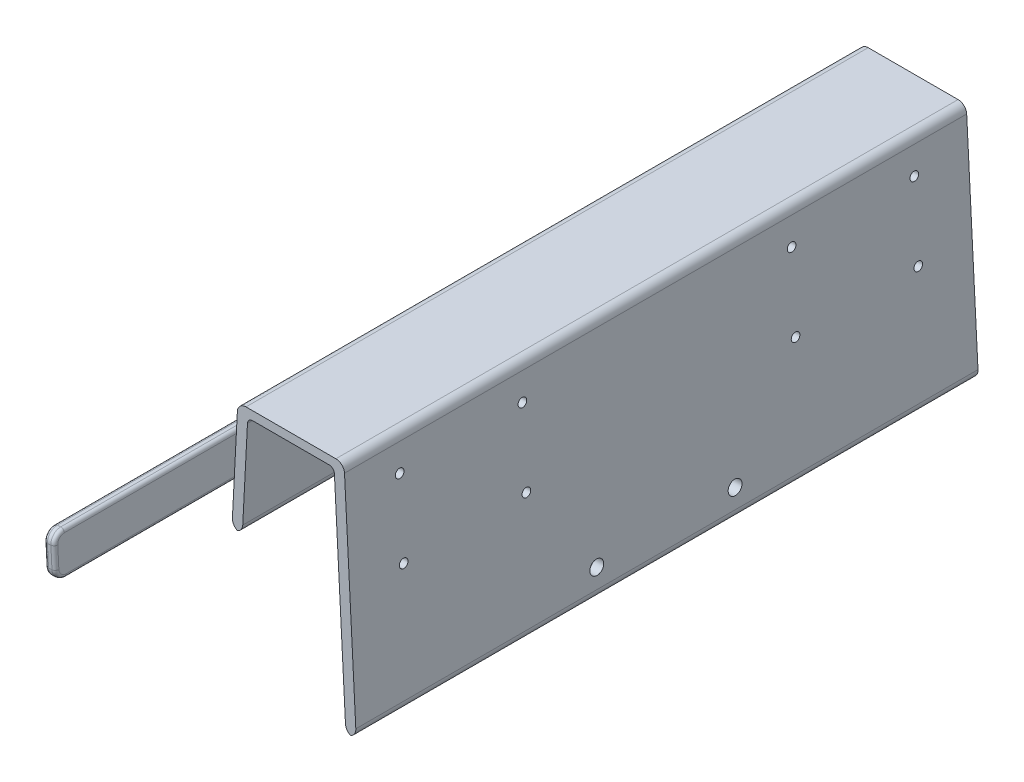
SolidWorks part; units mm, degrees
ref_plane "Front Plane" through (0, 0, 0) normal (0, 0, 1) x (1, 0, 0)
ref_plane "Top Plane" through (0, 0, 0) normal (0, 1, 0) x (1, 0, 0)
ref_plane "Right Plane" through (0, 0, 0) normal (1, 0, 0) x (0, 0, -1)
sketch "Sketch1" plane through (0, 0, 0) normal (0, 0, 1) x (1, 0, 0)
  line L0 (0, 0) -> (1.5701, 29.9589)
  line L1 (1.5701, 29.9589) -> (26.5701, 29.9589)
  line L2 (26.5701, 29.9589) -> (29.9719, -34.952)
  line L3 (0, 0) -> (-3.0041, 0)
  line L4 (-3.0041, 0) -> (-1.303, 32.4589)
  line L5 (-1.303, 32.4589) -> (29.4432, 32.4589)
  line L6 (29.4432, 32.4589) -> (32.976, -34.952)
  line L7 (32.976, -34.952) -> (29.9719, -34.952)
  dimension "D1" = 65
  dimension "D2" = 30
  dimension "D3" = 25
  dimension "D4" = 3
  dimension "D5" = 2.5
  dimension "D6" = 3
  dimension "D7" = 93
  dimension "D8" = 93
extrude "Boss-Extrude1" add sketch "Sketch1" against normal blind 180
sketch "Sketch2" plane through (31.059, 1.6277, 0) normal (0.9986, 0.0523, 0) x (0, 0, -1)
  line L0 (90, -36.63) -> (90, 30.8735) construction
  line L1 (180, -36.63) -> (0, -36.63) construction
  line L2 (180, 30.8735) -> (0, 30.8735) construction
  line L3 (90, 30.8735) -> (180, 30.8735) construction
  circle A0 centre (128.94, 20.8735) radius 1.25
  circle A1 centre (164.44, 20.8735) radius 1.25
  circle A2 centre (128.94, -1.1265) radius 1.25
  circle A3 centre (164.44, -1.1265) radius 1.25
  circle A4 centre (51.06, -1.1265) radius 1.25
  circle A5 centre (15.56, -1.1265) radius 1.25
  circle A6 centre (15.56, 20.8735) radius 1.25
  circle A7 centre (51.06, 20.8735) radius 1.25
  dimension "D1" = 38.94
  dimension "D2" = 35.5
  dimension "D3" = 22
  dimension "D4" = 35.5
  dimension "D5" = 22
  dimension "D6" = 10
  dimension "D7" = 10
extrude "Holder cut" cut sketch "Sketch2" against normal up to next contours A2 | A1 | A0 | A3 | A4 | A5 | A7 | A6
ref_plane "Plane1" through (0, 0, -90) normal (0, 0, 1) x (1, 0, 0)
sketch "Sketch4" plane through (31.059, 1.6277, 0) normal (0.9986, 0.0523, 0) x (0, 0, -1)
  line L0 (90, -36.63) -> (90, -39)
  line L1 (180, -36.63) -> (0, -36.63) construction
  line L2 (90, 44.55) -> (90, -44.55) construction
  circle A0 centre (110, -28.63) radius 2
  dimension "D3" = 8
  dimension "D2" = 20
extrude "Cut-Extrude2" cut sketch "Sketch4" against normal up to next contours A0
mirror "Mirror1" about plane through (0, 0, -90) normal (0, 0, 1) of "Cut-Extrude2"
fillet "Fillet2" radius 1.5 2 edges at (1.5701, 29.9589, -90) (26.5701, 29.9589, -90)
fillet "Fillet3" radius 2.5 2 edges at (-3.0041, 0, -90) (0, 0, -90)
ref_plane "Plate lower plane" through (-58.8177, -3.0825, 0) normal (0.9986, 0.0523, 0) x (0, 0, -1)
sketch "Sketch5" plane through (-58.8177, -3.0825, 0) normal (0.9986, 0.0523, 0) x (0, 0, -1)
  line L0 (180, -36.4727) -> (180, -24.4727)
  line L1 (180, 27.1038) -> (180, -36.4727) construction
  line L2 (180, -24.4727) -> (0, -24.4727)
  line L3 (0, 27.1038) -> (0, -36.4727) construction
  line L4 (0, -24.4727) -> (0, -36.4727)
  line L5 (0, -36.4727) -> (180, -36.4727)
  circle A0 centre (110, -28.63) radius 2
  circle A1 centre (70, -28.63) radius 2
  dimension "D1" = 12
extrude "Boss-Extrude2" add sketch "Sketch5" along normal blind 3 separate body
fillet "Fillet1" radius 3 4 edges at (-55.4109, -39.4268, -180) (-56.0389, -27.4432, -180) (-56.0389, -27.4432, 0) (-55.4109, -39.4268, 0)
fillet "Fillet4" radius 2.5 2 edges at (32.976, -34.952, -90) (29.9719, -34.952, -90)
fillet "Fillet5" radius 2.5 2 edges at (29.4432, 32.4589, -90) (-1.303, 32.4589, -90)
fillet "Fillet6" radius 1 16 edges at (-57.4909, -28.3992, -179.1213) (-57.2229, -33.5135, -180) (-56.9548, -38.6278, -179.1213) (-56.9089, -39.5053, -90) (-56.9548, -38.6278, -0.8787) (-57.2229, -33.5135, 0) (-57.4909, -28.3992, -0.8787) (-54.495, -28.2422, -179.1213) (-54.227, -33.3565, -180) (-53.959, -38.4708, -179.1213) (-53.913, -39.3483, -90) (-53.959, -38.4708, -0.8787) (-54.227, -33.3565, 0) (-54.495, -28.2422, -0.8787) (-57.5369, -27.5217, -90) (-54.541, -27.3647, -90)
